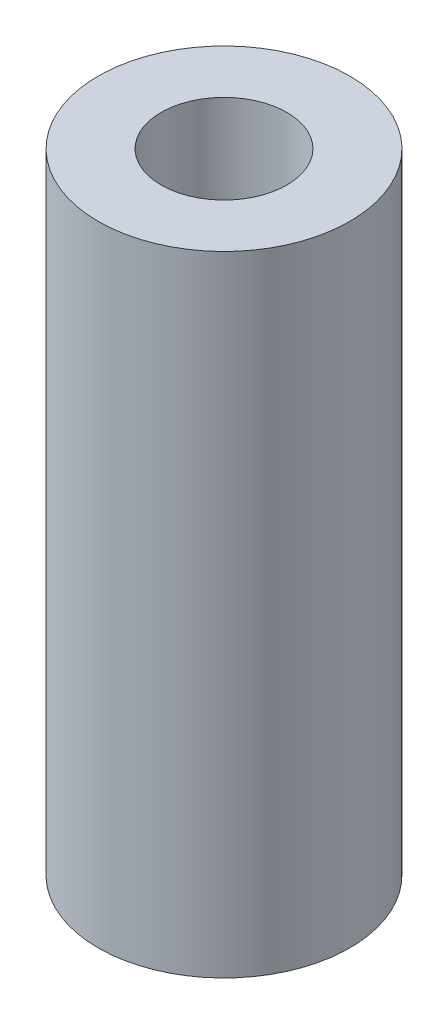
SolidWorks part; units mm, degrees
material "Brass"
ref_plane "Front Plane" through (0, 0, 0) normal (0, 0, 1) x (1, 0, 0)
ref_plane "Top Plane" through (0, 0, 0) normal (0, 1, 0) x (1, 0, 0)
ref_plane "Right Plane" through (0, 0, 0) normal (1, 0, 0) x (0, 0, -1)
sketch "Sketch1" plane through (0, 0, 0) normal (0, 1, 0) x (1, 0, 0)
  circle A0 centre (0, 0) radius 1
  circle A1 centre (0, 0) radius 0.5
  dimension "D1" = 2
  dimension "D2" = 1
extrude "Boss-Extrude1" add sketch "Sketch1" along normal blind 5
scale "Scale1" scale about centroid uniform scaling yes scale factor 6
